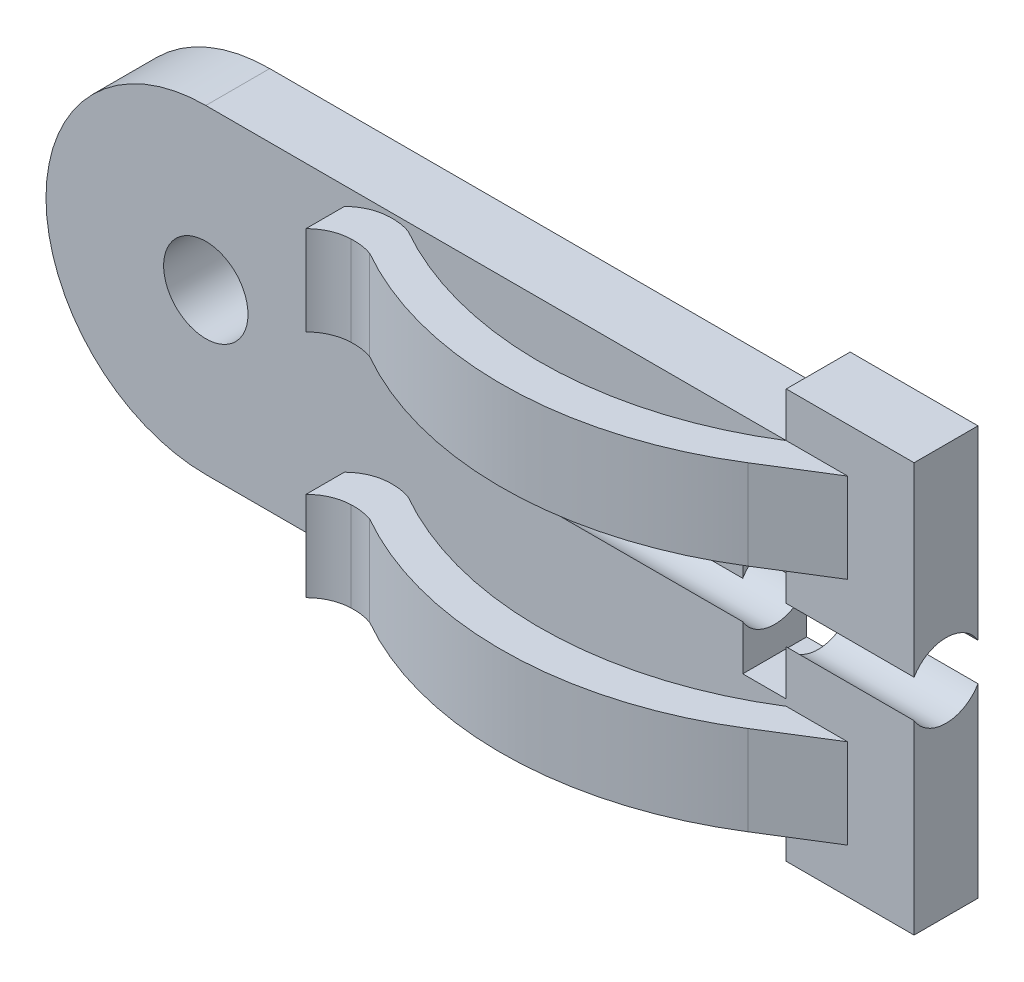
SolidWorks part; units mm, degrees
ref_plane "Front Plane" through (0, 0, 0) normal (0, 0, 1) x (1, 0, 0)
ref_plane "Top Plane" through (0, 0, 0) normal (0, 1, 0) x (1, 0, 0)
ref_plane "Right Plane" through (0, 0, 0) normal (1, 0, 0) x (0, 0, -1)
sketch "Sketch1" plane through (0, 0, 0) normal (0, 0, 1) x (1, 0, 0)
  line L0 (0, -6.25) -> (22.7, -6.25)
  line L1 (-12.7, 12.7) -> (12.7, 12.7)
  line L2 (-12.7, 12.7) -> (-12.7, -12.7)
  line L3 (-12.7, -12.7) -> (12.7, -12.7)
  line L4 (12.7, 12.7) -> (12.7, -12.7)
  line L5 (0, 6.25) -> (22.7, 6.25)
  line L6 (22.7, 6.25) -> (22.7, -6.25)
  circle A0 centre (0, 0) radius 1.65
  arc A1 (0, 6.25) -> (0, -6.25) centre (0, 0) ccw
  dimension "D1" = 3.3
  dimension "D3" = 25.4
  dimension "D4" = 25.4
  dimension "D5" = 12.7
  dimension "D6" = 12.7
  dimension "D7" = 10
extrude "Boss-Extrude1" add sketch "Sketch1" along normal blind 2.5 contours L5 A1 L0 L4 A0 | L6 L5 L4 L0 region at (3.9956, 0, 0) region at (17.7, 0, 0)
sketch "Sketch2" plane through (0, 0, 2.5) normal (0, 0, 1) x (1, 0, 0)
  line L1 (22.7, -8) -> (27.7, -8)
  line L2 (22.7, -8) -> (22.7, 8)
  line L3 (22.7, 8) -> (27.7, 8)
  line L4 (27.7, -8) -> (27.7, 8)
  circle A0 centre (0, 0) radius 1.65 construction
  dimension "D1" = 5
  dimension "D2" = 16
  dimension "D3" = 8
extrude "Boss-Extrude2" add sketch "Sketch2" against normal blind 2.5
sketch "Sketch3" plane through (0, 0, 2.5) normal (0, 0, 1) x (1, 0, 0)
  line L0 (22.7, 8) -> (22.7, 6.25) construction
  line L1 (22.7, 2.5) -> (21, 2.5)
  line L2 (22.7, 2.5) -> (22.7, -2.5)
  line L3 (22.7, -2.5) -> (21, -2.5)
  line L4 (21, 2.5) -> (21, -2.5)
  circle A0 centre (0, 0) radius 1.65 construction
  dimension "D1" = 1.7
  dimension "D2" = 0
  dimension "D3" = 5
  dimension "D4" = 2.5
extrude "Cut-Extrude1" cut sketch "Sketch3" against normal through all
sketch "Sketch6" plane through (27.7, 0, 0) normal (1, 0, 0) x (0, 0, -1)
  line L0 (-2.5, -8) -> (-2.5, 8) construction
  line L1 (0, -8) -> (-2.5, -8) construction
  line L2 (0, 8) -> (-2.5, 8) construction
  circle A0 centre (-1.25, 0) radius 1.45
  point P6 (-1.25, 8)
  dimension "D4" = 2.9
  dimension "D1" = 1.25
  dimension "D2" = 8
  dimension "D3" = 8
extrude "Cut-Extrude3" cut sketch "Sketch6" against normal blind 16.7
sketch "Sketch7" plane through (0, -6.25, 0) normal (0, -1, 0) x (1, 0, 0)
  line L1 (6.1299, 3.2107) -> (6.1299, 4.7107)
  line L3 (22.7, 4) -> (22.7, 2.5)
  arc A0 (22.7, 2.5) -> (8.2067, 2.7997) centre (15.2027, -9.4701) ccw
  arc A1 (7.3606, 2.6809) -> (6.1299, 3.2107) centre (7.409, 4.4878) cw
  arc A2 (7.3606, 2.6809) -> (8.2067, 2.7997) centre (7.4758, 4.9321) ccw
  arc A3 (7.3606, 4.1809) -> (6.1299, 4.7107) centre (7.409, 5.9878) cw
  arc A4 (22.7, 4) -> (8.2067, 4.2997) centre (15.2027, -7.9701) ccw
  arc A5 (7.3606, 4.1809) -> (8.2067, 4.2997) centre (7.4758, 6.4321) ccw
  dimension "D3" = 2
  dimension "D1" = 1.5
extrude "Boss-Extrude3" add sketch "Sketch7" against normal blind 3.5 separate body
sketch "Sketch9" plane through (0, -6.25, 0) normal (0, -1, 0) x (1, 0, 0)
  line L0 (22.7, 4) -> (25.1049, 2.5)
  line L1 (25.1049, 2.5) -> (22.7, 2.5)
  line L2 (22.7, 2.5) -> (22.7, 4)
extrude "Boss-Extrude5" add sketch "Sketch9" against normal blind 3.5 separate body
combine bodies "Combine1" operation type add bodies to combine 111 106
ref_plane "Plane1" through (0, 0, 0) normal (0, -1, 0) x (-1, 0, 0)
mirror "Mirror5" about plane through (0, 0, 0) normal (0, -1, 0) of bodies 112
